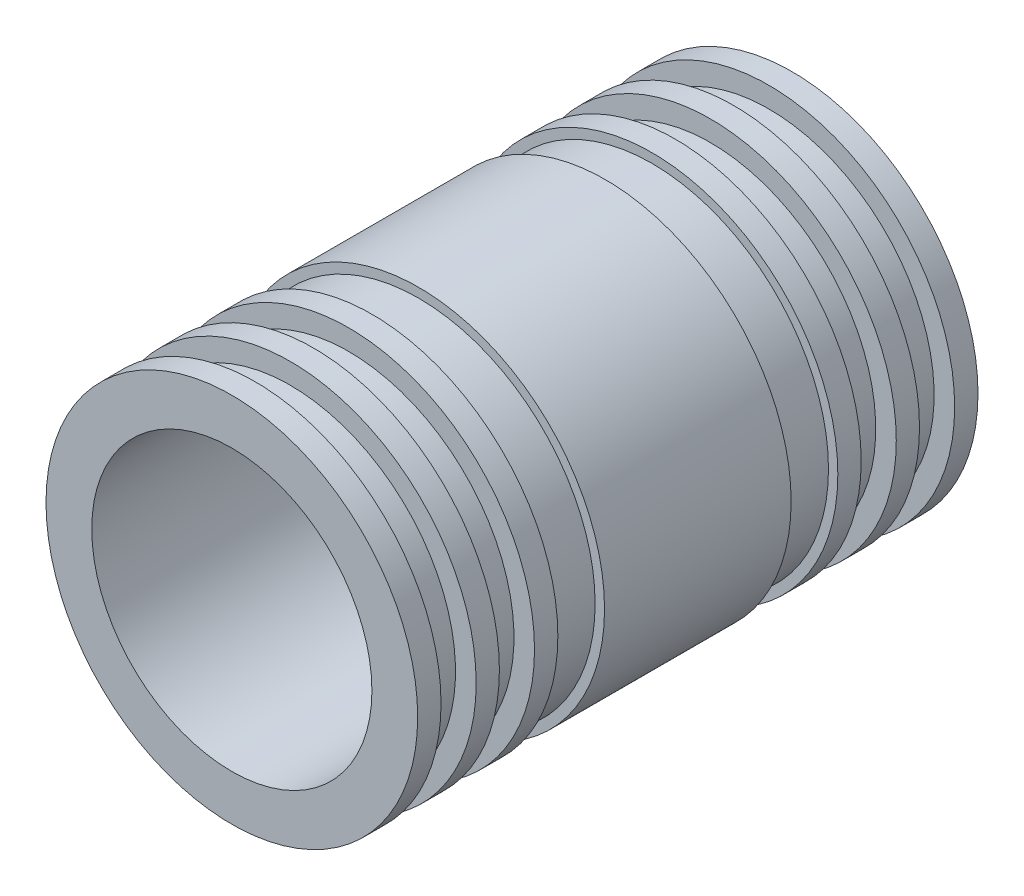
SolidWorks part; units mm, degrees
material "6061 Alloy"
ref_plane "Front Plane" through (0, 0, 0) normal (0, 0, 1) x (1, 0, 0)
ref_plane "Top Plane" through (0, 0, 0) normal (0, 1, 0) x (1, 0, 0)
ref_plane "Right Plane" through (0, 0, 0) normal (1, 0, 0) x (0, 0, -1)
sketch "Sketch1" plane through (0, 0, 0) normal (0, 0, 1) x (1, 0, 0)
  circle A0 centre (0, 0) radius 25.273
  dimension "D1" = 50.546
extrude "Boss-Extrude1" add sketch "Sketch1" along normal blind 76.2
sketch "Sketch5" plane through (0, 0, 76.2) normal (0, 0, 1) x (1, 0, 0)
  circle A0 centre (0, 0) radius 19.05
  dimension "D1" = 38.1
extrude "Cut-Extrude2" cut sketch "Sketch5" against normal blind 76.2
ref_plane "Plane1" through (0, 0, 76.2) normal (-1, 0, 0) x (0, 1, 0)
ref_plane "Plane2" through (0, 0, 76.2) normal (-1, 0, 0) x (0, 1, 0)
ref_plane "Plane3" through (0, 0, 76.2) normal (-1, 0, 0) x (0, 1, 0)
ref_plane "Plane4" through (0, 0, 76.2) normal (-1, 0, 0) x (0, 1, 0)
sketch "Groove" plane through (0, 0, 0) normal (1, 0, 0) x (0, 0, -1)
  line L0 (0, 25.273) -> (-76.2, 25.273) construction
  line L1 (-76.2, 25.273) -> (-76.2, -25.273) construction
  line L2 (-73.025, 25.273) -> (-73.025, 22.479)
  line L3 (-73.025, 22.479) -> (-68.2625, 22.479)
  line L4 (-68.2625, 22.479) -> (-68.2447, 25.273)
  line L5 (-68.2447, 25.273) -> (-65.0875, 25.273)
  line L6 (-65.0875, 25.273) -> (-65.0875, 22.479)
  line L7 (-65.0875, 22.479) -> (-60.3123, 22.479)
  line L8 (-60.3123, 22.479) -> (-60.3123, 25.273)
  line L9 (-60.3123, 25.273) -> (-57.1373, 25.273)
  line L10 (-57.1373, 25.273) -> (-57.1373, 24.003)
  line L11 (-57.1373, 24.003) -> (-50.8, 24.003)
  line L12 (-50.8, 24.003) -> (-50.7873, 25.273)
  line L13 (-50.7873, 25.273) -> (-50.7873, 27.7239)
  line L14 (-50.7873, 27.7239) -> (-73.025, 27.7239)
  line L15 (-73.025, 27.7239) -> (-73.025, 25.273)
  line L16 (-38.1, 25.273) -> (-38.1, -25.3913) construction
  line L17 (-3.175, 27.7239) -> (-3.175, 25.273)
  line L18 (-25.4127, 27.7239) -> (-3.175, 27.7239)
  line L19 (-25.4127, 25.273) -> (-25.4127, 27.7239)
  line L20 (-25.4, 24.003) -> (-25.4127, 25.273)
  line L21 (-19.0627, 24.003) -> (-25.4, 24.003)
  line L22 (-19.0627, 25.273) -> (-19.0627, 24.003)
  line L23 (-15.8877, 25.273) -> (-19.0627, 25.273)
  line L24 (-15.8877, 22.479) -> (-15.8877, 25.273)
  line L25 (-11.1125, 22.479) -> (-15.8877, 22.479)
  line L26 (-11.1125, 25.273) -> (-11.1125, 22.479)
  line L27 (-7.9553, 25.273) -> (-11.1125, 25.273)
  line L28 (-7.9375, 22.479) -> (-7.9553, 25.273)
  line L29 (-3.175, 22.479) -> (-7.9375, 22.479)
  line L30 (-3.175, 25.273) -> (-3.175, 22.479)
  point P0 (-73.025, 25.273)
  point P1 (-68.2625, 25.273)
  point P4 (-68.2447, 25.273)
  point P5 (-65.0875, 25.273)
  point P7 (-60.3123, 25.273)
  point P9 (-57.1373, 25.273)
  point P10 (-50.7873, 25.273)
  point P11 (-50.8, 25.273)
  point P14 (-38.1, 25.273)
  point P27 (-38.1, -25.3913)
  point P44 (-25.4, 25.273)
  point P45 (-7.9375, 25.273)
  dimension "D1" = 3.175
  dimension "D2" = 4.7625
  dimension "D3" = 3.175
  dimension "D4" = 4.7752
  dimension "D5" = 3.175
  dimension "D6" = 2.794
  dimension "D7" = 25.4
  dimension "D8" = 2.794
  dimension "D9" = 1.27
ref_plane "Plane9" through (0, 0, 60.3123) normal (0, 0, 1) x (1, 0, 0)
sketch "groove path" plane through (0, 0, 60.3123) normal (0, 0, 1) x (1, 0, 0)
  circle A0 centre (0, 0) radius 25.273 construction
  circle A1 centre (0, 0) radius 25.273
sweep "Cut-Sweep4" cut profiles "Groove" path "groove path"
